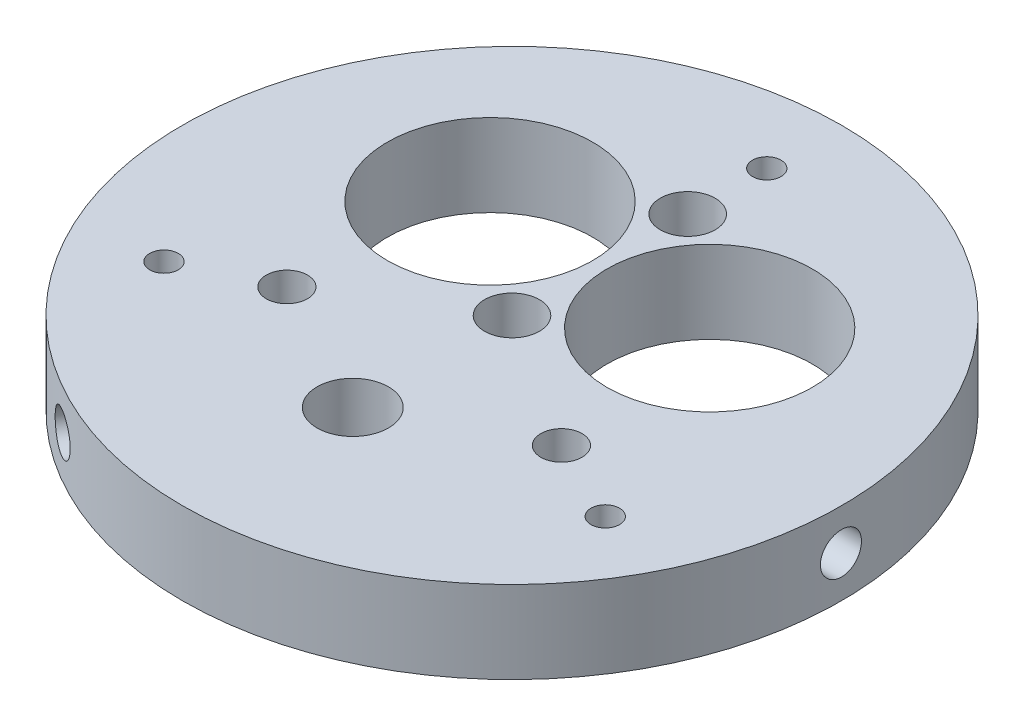
SolidWorks part; units mm, degrees
material "G10 Fiberglass"
ref_plane "Front Plane" through (0, 0, 0) normal (0, 0, 1) x (1, 0, 0)
ref_plane "Top Plane" through (0, 0, 0) normal (0, 1, 0) x (1, 0, 0)
ref_plane "Right Plane" through (0, 0, 0) normal (1, 0, 0) x (0, 0, -1)
sketch "Sketch1" plane through (0, 0, 0) normal (0, 1, 0) x (1, 0, 0)
  circle A0 centre (0, 0) radius 38.1127
  dimension "D1" = 76.2254
extrude "Boss-Extrude1" add sketch "Sketch1" along normal blind 9.525
sketch "Sketch2" plane through (0, 9.525, 0) normal (0, 1, 0) x (1, 0, 0)
  line L0 (12.7, 10.16) -> (-12.7, 10.16) construction
  line L3 (0, 6.35) -> (0, -19.05) construction
  line L4 (-14.6012, 35.2049) -> (-10.7695, 36.5595) construction
  line L5 (-14.6012, 35.2049) -> (-11.9555, 27.7213) construction
  line L6 (-10.7695, 36.5595) -> (-8.1239, 29.0759) construction
  line L7 (-11.9555, 27.7213) -> (-8.1239, 29.0759) construction
  line L8 (37.9022, -4.9723) -> (30.0984, -3.5218) construction
  line L9 (37.9022, -4.9723) -> (37.1595, -8.9679) construction
  line L10 (37.1595, -8.9679) -> (29.3557, -7.5173) construction
  line L11 (30.0984, -3.5218) -> (29.3557, -7.5173) construction
  line L12 (-23.144, -30.353) -> (-17.9858, -24.32) construction
  line L13 (-23.144, -30.353) -> (-26.2329, -27.712) construction
  line L14 (-26.2329, -27.712) -> (-21.0747, -21.679) construction
  line L15 (-17.9858, -24.32) -> (-21.0747, -21.679) construction
  line L16 (0, 10.16) -> (0, -18.415) construction
  line L17 (-12.7, 10.16) -> (12.7, 10.16) construction
  line L18 (-12.7, 24.13) -> (12.7, 24.13) construction
  line L19 (-12.7, -3.81) -> (12.7, -3.81) construction
  circle A0 centre (0, 0) radius 29.464 construction
  circle A1 centre (0, 29.464) radius 1.651
  circle A2 centre (25.5166, -14.732) radius 1.651
  circle A3 centre (-25.5166, -14.732) radius 1.651
  circle A4 centre (0, -18.415) radius 4.1275
  circle A7 centre (0, 0) radius 38.1127 construction
  circle A8 centre (-12.7, 10.16) radius 11.8745
  circle A9 centre (12.7, 10.16) radius 11.8745
  circle A10 centre (0, 20.32) radius 3.175
  circle A11 centre (0, 0) radius 3.175
  arc A12 (-12.7, 24.13) -> (-12.7, -3.81) centre (-12.7, 10.16) ccw construction
  arc A13 (12.7, -3.81) -> (12.7, 24.13) centre (12.7, 10.16) ccw construction
  point P11 (0, 0)
  point P36 (0.0524, -0.0401)
  point P38 (0, 10.16)
  dimension "D1" = 3.302
  dimension "D2" = 58.928
  dimension "D11" = 8.255
  dimension "D4" = 23.749
  dimension "D5" = 23.749
  dimension "D13" = 6.35
  dimension "D14" = 6.35
  dimension "D7" = 4.064
  dimension "D8" = 7.9375
  dimension "D6" = 10.16
  dimension "D10" = 25.4
  dimension "D12" = 28.575
  dimension "D15" = 27.94
  dimension "D17" = 3.81
  dimension "D16" = 3.81
  dimension "D3" = 3
  dimension "D9" = 3
extrude "Cut-Extrude1" cut sketch "Sketch2" against normal through all contours A1 | A3 | A2 | A4 | A8 | A9 | A10 | A11 region at (0, 9.525, -29.464) region at (25.5166, 9.525, 14.732) region at (-25.5166, 9.525, 14.732) region at (0, 9.525, 18.415) region at (-12.7, 9.525, -10.16) region at (12.7, 9.525, -10.16) region at (0, 9.525, -20.32) region at (0, 9.525, 0)
ref_plane "Plane1" through (-19.0563, 0, -33.0066) normal (-0.5, 0, -0.866) x (0, -1, 0)
sketch "Sketch4" plane through (-19.0563, 0, -33.0066) normal (-0.5, 0, -0.866) x (0, -1, 0)
  circle A0 centre (-4.7625, 0) radius 2.3749
  dimension "D1" = 4.7625
  dimension "D2" = 4.7498
extrude "Cut-Extrude2" cut sketch "Sketch4" against normal blind 6.35
ref_axis "Axis1" through (0, 10.0012, 0) along (0, -1, 0)
pattern_circular "CirPattern1" count 3 over 360 about axis through (0, 10.0012, 0) along (0, -1, 0) of "Cut-Extrude2"
pattern_circular "CirPattern2" [suppressed] count 2 over 360 about axis through (0, 10.0012, 0) along (0, -1, 0) of bodies 104
sketch "Sketch5" plane through (0, 9.525, 0) normal (0, 1, 0) x (1, 0, 0)
  line L0 (-15.875, -10.16) -> (15.875, -10.16) construction
  line L1 (0, 0) -> (0, -10.16) construction
  circle A0 centre (-15.875, -10.16) radius 2.3813
  circle A1 centre (15.875, -10.16) radius 2.3813
  dimension "D1" = 4.7625
  dimension "D2" = 4.7625
  dimension "D3" = 31.75
  dimension "D4" = 10.16
extrude "Cut-Extrude3" cut sketch "Sketch5" against normal through all both
equation "\"D5@Sketch2\"=\"D4@Sketch2\""
equation "\"D4@Sketch2\"=0.925in+0.01"
equation "\"D13@Sketch2\"=\"D14@Sketch2\""
equation "\"D16@Sketch2\"=\"D17@Sketch2\""
